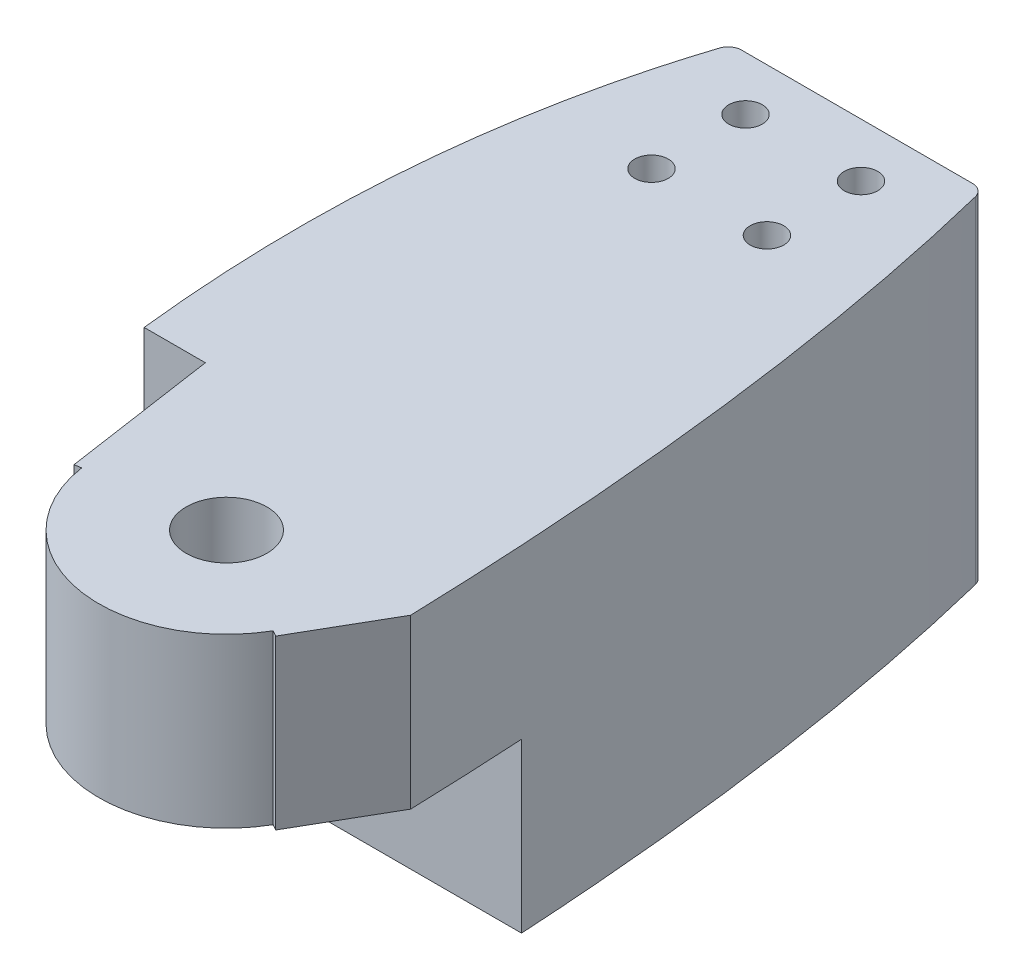
SolidWorks part; units mm, degrees
ref_plane "정면" through (0, 0, 0) normal (0, 0, 1) x (1, 0, 0)
ref_plane "윗면" through (0, 0, 0) normal (0, 1, 0) x (1, 0, 0)
ref_plane "우측면" through (0, 0, 0) normal (1, 0, 0) x (0, 0, -1)
sketch "스케치1" plane through (0, 0, 0) normal (0, 0, 1) x (1, 0, 0)
  line L1 (-12.5, -12.5) -> (12.5, -12.5)
  line L2 (-12.5, -12.5) -> (-12.5, 12.5)
  line L3 (-12.5, 12.5) -> (12.5, 12.5)
  line L4 (12.5, -12.5) -> (12.5, 12.5)
  line L5 (-12.5, -12.5) -> (12.5, 12.5) construction
  line L6 (-12.5, 12.5) -> (12.5, -12.5) construction
  point P0 (0, 0)
  dimension "D1" = 25
extrude "보스-돌출1" add sketch "스케치1" along normal blind 59.6073 contours L3 L4 L1 L2
sketch "스케치6" plane through (0, -12.5, 0) normal (0, -1, 0) x (1, 0, 0)
  line L0 (-12.5, 0) -> (12.5, 0) construction
  line L2 (-12.5, 59.6073) -> (-21.1491, 25.9147) construction
  line L4 (-21.1491, 25.9147) -> (-12.5, 0) construction
  line L6 (6.1913, 0) -> (12.5, 24.9535) construction
  line L9 (12.5, 24.9535) -> (12.5, 59.6073) construction
  line L11 (6.1913, 0) -> (-12.5, 0)
  line L12 (-12.5, 59.6073) -> (-12.5, 0)
  line L13 (12.5, 59.6073) -> (-12.5, 59.6073)
  spline S0 degree 2 poles (-12.5, 59.6073) (-21.1491, 25.9147) (-12.5, 0) knots 0 0 0 1 1 1
  spline S1 degree 2 poles (6.1913, 0) (12.5, 24.9535) (12.5, 59.6073) knots 0 0 0 1 1 1
  line M2 (-12.5, 0) -> (12.5, 0)
  line M4 (12.5, 59.6073) -> (-12.5, 59.6073)
  line M5 (-12.5, 59.6073) -> (-12.5, 0)
extrude "보스-돌출2" add sketch "스케치6" against normal blind 25 contours S0 M5 region at (-14.2298, -12.5, 29.0259)
extrude "컷-돌출4" cut sketch "스케치6<3>" against normal blind 25 flip side to cut contours S0 M5 | S1 M2 M4 M5 region at (-0.893, -12.5, 31.1107) region at (-14.2298, -12.5, 29.0259)
sketch "스케치6<3>" plane through (0, -12.5, 0) normal (0, -1, 0) x (1, 0, 0) same geometry as "스케치6"
sketch "스케치2" plane through (0, 12.5, 0) normal (0, 1, 0) x (1, 0, 0)
  line L0 (-12.5, -59.6073) -> (12.5, -59.6073) construction
  circle A0 centre (0, -50.1073) radius 3
  dimension "D1" = 6
  dimension "D2" = 9.5
extrude "컷-돌출1" cut sketch "스케치2" against normal blind 36.3445 contours A0
sketch "스케치4" plane through (0, 0, 59.6073) normal (0, 0, 1) x (1, 0, 0)
  line L0 (-12.5, -12.5) -> (12.5, -12.5) construction
  line L6 (-26.7211, 0) -> (19.2593, 0)
  line L7 (-26.7211, 0) -> (-26.7211, -12.5)
  line L8 (-26.7211, -12.5) -> (19.2593, -12.5)
  line L9 (19.2593, 0) -> (19.2593, -12.5)
  line L10 (-26.7211, 0) -> (19.2593, -12.5) construction
  line L11 (-26.7211, -12.5) -> (19.2593, 0) construction
  point P0 (-3.7309, -6.25)
  dimension "D1" = 12.5
extrude "컷-돌출2" cut sketch "스케치4" against normal blind 19.5
sketch "스케치7" plane through (0, 0, 0) normal (0, -1, 0) x (1, 0, 0)
  line L0 (0, 50.1073) -> (8.2272, 54.8573)
  line L1 (0, 50.1073) -> (0, 75.6875) construction
  line L2 (8.2272, 54.8573) -> (12.3073, 47.7905) construction
  line L3 (0, 59.6073) -> (12.5, 59.6073)
  line L6 (8.6603, 55.1073) -> (12.3376, 48.7379)
  line L7 (8.2272, 54.8573) -> (8.6603, 55.1073)
  line L8 (8.6603, 55.1073) -> (12.7403, 48.0405) construction
  line L10 (-12.5, 59.6073) -> (0, 59.6073)
  line L11 (0, 50.1073) -> (-9.894, 51.5593)
  line L12 (-9.894, 51.5593) -> (-11.5747, 40.1073)
  line L13 (11.9569, 40.1073) -> (-16.1309, 40.1073) construction
  line L14 (-11.5747, 40.1073) -> (-16.1309, 40.1073)
  arc A0 (8.2272, 54.8573) -> (0, 59.6073) centre (0, 50.1073) ccw
  arc A1 (0, 59.6073) -> (-9.3993, 51.4867) centre (0, 50.1073) ccw
  parabola Q0 (11.9569, 40.1073) -> (12.5, 59.6073) focus (-44.0818, -27.3931) apex (-27.2631, -53.2536) construction
  parabola Q1 (11.9569, 40.1073) -> (12.5, 59.6073) focus (-44.0818, -27.3931) apex (-27.2631, -53.2536) construction
  parabola Q2 (12.3376, 48.7379) -> (12.5, 59.6073) focus (-44.0818, -27.3931) apex (-27.2631, -53.2536)
  parabola Q3 (11.9569, 40.1073) -> (12.5, 59.6073) focus (-44.0818, -27.3931) apex (-27.2631, -53.2536) construction
  parabola Q4 (11.9569, 40.1073) -> (12.5, 59.6073) focus (-44.0818, -27.3931) apex (-27.2631, -53.2536) construction
  parabola Q5 (-12.5, 59.6073) -> (-16.1309, 40.1073) focus (25.8894, 8.6535) apex (-9.6413, -7.3223) construction
  parabola Q6 (-12.5, 59.6073) -> (-16.1309, 40.1073) focus (25.8894, 8.6535) apex (-9.6413, -7.3223) construction
  parabola Q7 (-12.5, 59.6073) -> (-16.1309, 40.1073) focus (25.8894, 8.6535) apex (-9.6413, -7.3223) construction
  parabola Q8 (-12.5, 59.6073) -> (-16.1309, 40.1073) focus (25.8894, 8.6535) apex (-9.6413, -7.3223)
  spline M3 degree 2 poles (-12.5, 59.6073) (-21.1491, 25.9147) (-12.5, 0) knots 0 0 0 1 1 1 only from (-12.5, 59.6073) to (-16.1309, 40.1073)
  line M4 (-16.1309, 40.1073) -> (11.9569, 40.1073)
  line M6 (12.5, 59.6073) -> (-12.5, 59.6073)
  dimension "D1" = 19
  dimension "D2" = 60
  dimension "D3" = 0.5
  dimension "D4" = 0.5
extrude "컷-돌출5" cut sketch "스케치7" against normal blind 17 contours A0 L0 Q2 M6 | A1 L12 L11 M6 M3 M4 region at (9.5049, 0, 56.3506) region at (-11.5115, 0, 50.8944)
fillet "필렛1" radius 1 2 edges at (6.1913, 0, 0) (-12.5, 0, 0)
sketch "스케치8" plane through (0, 0, 0) normal (0, 1, 0) x (1, 0, 0)
  line L0 (-11.776, 0) -> (5.4107, 0) construction
  line L1 (-11.776, 0) -> (5.4107, 0) construction
  line L2 (-3.1827, 0) -> (-3.1827, -19.0234) construction
  line L3 (-9.776, 0) -> (-5.1827, 0)
  line L4 (3.4107, 0) -> (-1.1827, 0)
  line L5 (3.4107, 0) -> (3.4107, -15)
  line L6 (3.4107, -15) -> (-1.1827, -15)
  line L7 (-1.1827, 0) -> (-1.1827, -15)
  line L8 (-9.776, 0) -> (-9.776, -15)
  line L9 (-5.1827, 0) -> (-5.1827, -15)
  line L10 (-9.776, -15) -> (-5.1827, -15)
  line L11 (3.4107, -7.5) -> (-1.1827, -7.5) construction
  circle A0 centre (1.114, -4) radius 1.25
  circle A1 centre (1.114, -11) radius 1.25
  circle A2 centre (-7.4794, -4) radius 1.25
  circle A3 centre (-7.4794, -11) radius 1.25
  dimension "D4" = 2.5
  dimension "D1" = 2
  dimension "D2" = 2
  dimension "D3" = 15
  dimension "D5" = 4
extrude "컷-돌출6" cut sketch "스케치8" against normal blind 20 and the other way blind 22 contours A0 | A1 | A2 | A3
extrude "컷-돌출7" cut sketch "스케치8<3>" against normal blind 10 and the other way blind 10 contours L5 L6 L7 L4 | L9 L10 L8 L3
sketch "스케치8<3>" plane through (0, 0, 0) normal (0, 1, 0) x (1, 0, 0) same geometry as "스케치8"
